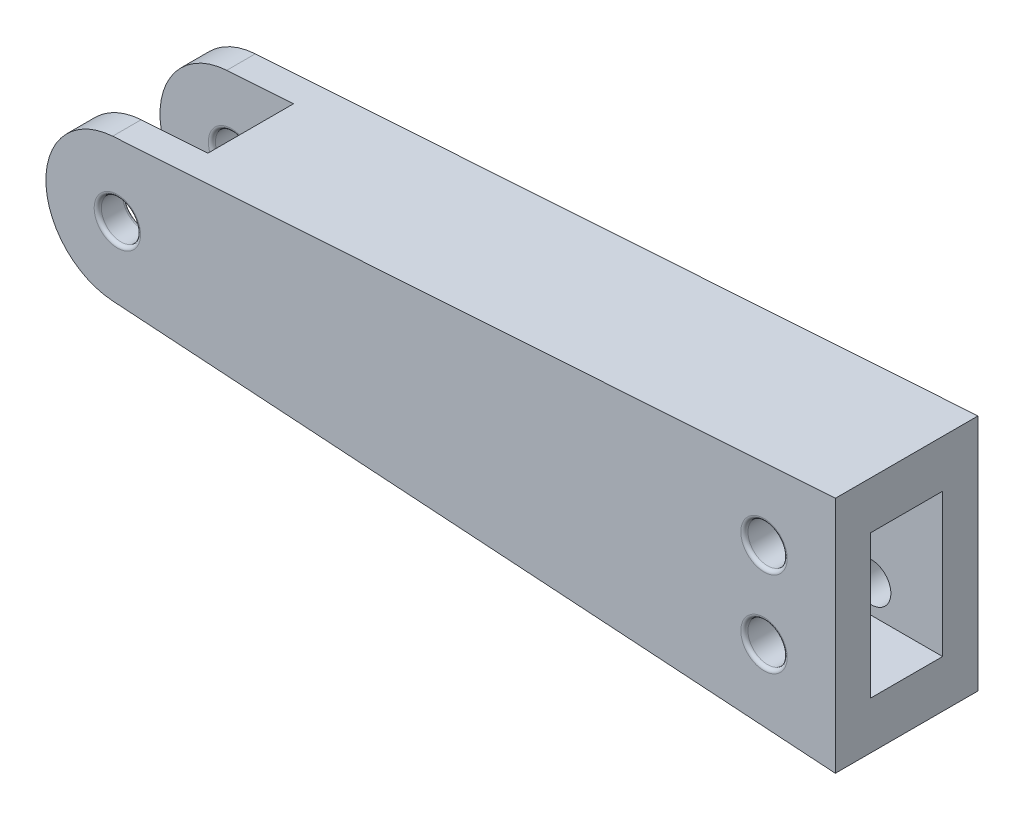
SolidWorks part; units mm, degrees
ref_plane "Front Plane" through (0, 0, 0) normal (0, 0, 1) x (1, 0, 0)
ref_plane "Top Plane" through (0, 0, 0) normal (0, 1, 0) x (1, 0, 0)
ref_plane "Right Plane" through (0, 0, 0) normal (1, 0, 0) x (0, 0, -1)
sketch "Sketch1" plane through (0, 0, 0) normal (0, 0, 1) x (1, 0, 0)
  line L0 (-50, 16.6955) -> (-151.3109, 10)
  line L1 (43.0973, 0) -> (50043.0973, 0) construction
  line L2 (0, 21.9801) -> (0, 50021.9801) construction
  line L3 (-50, -16.6955) -> (-151.3109, -10)
  line L4 (-50, 16.6955) -> (-50, -16.6955)
  line L5 (-50, 16.6955) -> (-50, -16.6955) construction
  line L6 (-6.5945, 19.5642) -> (-50, 16.6955) construction
  line L7 (-120.65, 129.451) -> (-120.65, -205.549) construction
  arc A0 (-151.3109, 10) -> (-151.3109, -10) centre (-150.65, 0) ccw
  point P9 (0, 0)
  point P10 (0, 0)
  point P14 (-156.2476, 0)
  dimension "D1" = 30
extrude "Boss-Extrude1" add sketch "Sketch1" along normal up to surface (20 mm away) contours L0 A0 L3 L4 region at (-99.4054, 0, 0)
sketch "Sketch2" plane through (-50, 0, 0) normal (1, 0, 0) x (0, 0, -1)
  line L1 (-4.965, -10.035) -> (-15.035, -10.035)
  line L2 (-4.965, -10.035) -> (-4.965, 10.035)
  line L3 (-4.965, 10.035) -> (-15.035, 10.035)
  line L4 (-20, 16.6955) -> (-20, -16.6955)
  line L5 (-20, -16.6955) -> (0, -16.6955)
  line L6 (0, -16.6955) -> (0, 16.6955)
  line L7 (0, 16.6955) -> (-20, 16.6955)
  line L8 (-20, 16.6955) -> (-20, -16.6955) construction
  line L9 (-20, -16.6955) -> (0, -16.6955) construction
  line L10 (0, -16.6955) -> (0, 16.6955) construction
  line L11 (0, 16.6955) -> (-20, 16.6955) construction
  line L12 (-15.035, -10.035) -> (-15.035, 10.035)
  line L13 (-4.965, -10.035) -> (-15.035, 10.035) construction
  line L14 (-4.965, 10.035) -> (-15.035, -10.035) construction
  point P2 (-10, 0)
  point P8 (-10, -16.6955)
  point P9 (-10, 0)
  dimension "D2" = 20.07
  dimension "D3" = 10.07
  dimension "D1" = 0
extrude "Cut-Extrude1" cut sketch "Sketch2" against normal blind 20
sketch "Sketch4" plane through (0, 0, 0) normal (0, 1, 0) x (1, 0, 0)
  line L0 (-160.6718, 0) -> (-160.6718, -20) construction
  line L1 (-160.6718, -4) -> (-141.95, -4)
  line L2 (-160.6718, -4) -> (-160.6718, -16)
  line L3 (-160.6718, -16) -> (-141.95, -16)
  line L4 (-141.95, -4) -> (-141.95, -16)
  line L5 (-160.6718, -4) -> (-141.95, -16) construction
  line L6 (-160.6718, -16) -> (-141.95, -4) construction
  line L7 (-160.6718, 0) -> (-160.6718, -20) construction
  line L8 (-151.3109, 0) -> (-160.6718, 0) construction
  line L9 (-151.3109, -20) -> (-151.3109, 0) construction
  point P4 (-151.3109, -10)
  point P7 (0, 0)
  point P8 (-151.3109, 4.1651)
  point P9 (-154.7421, 3.8187)
  point P10 (0, 0)
  point P11 (0, 0)
  point P12 (-160.6718, -10)
  point P17 (-151.3109, -4)
  dimension "D1" = 4
extrude "Cut-Extrude2" cut sketch "Sketch4" against normal through all both and the other way through all
sketch "Sketch5" plane through (0, 0, 0) normal (0, 0, -1) x (-1, 0, 0)
  circle A0 centre (150.65, 0) radius 2.75
  dimension "D1" = 5.5
extrude "Cut-Extrude3" cut sketch "Sketch5" against normal through all
sketch "Sketch6" plane through (0, 0, 0) normal (0, 0, -1) x (-1, 0, 0)
  line L0 (50, -16.6955) -> (50, 16.6955) construction
  line L1 (0, 0) -> (50000, 0) construction
  circle A0 centre (60, -6) radius 2.75
  circle A1 centre (60, 6) radius 2.75
  dimension "D1" = 5.5
  dimension "D2" = 10
  dimension "D3" = 6
extrude "Cut-Extrude4" cut sketch "Sketch6" against normal through all
fillet "Fillet1" radius 0.5 8 edges at (-147.9, 0, 16) (-153.4, 0, 20) (-153.4, 0, 4) (-153.4, 0, 0) (-57.25, 6, 0) (-57.25, 6, 20) (-62.75, -6, 0) (-62.75, -6, 20)
